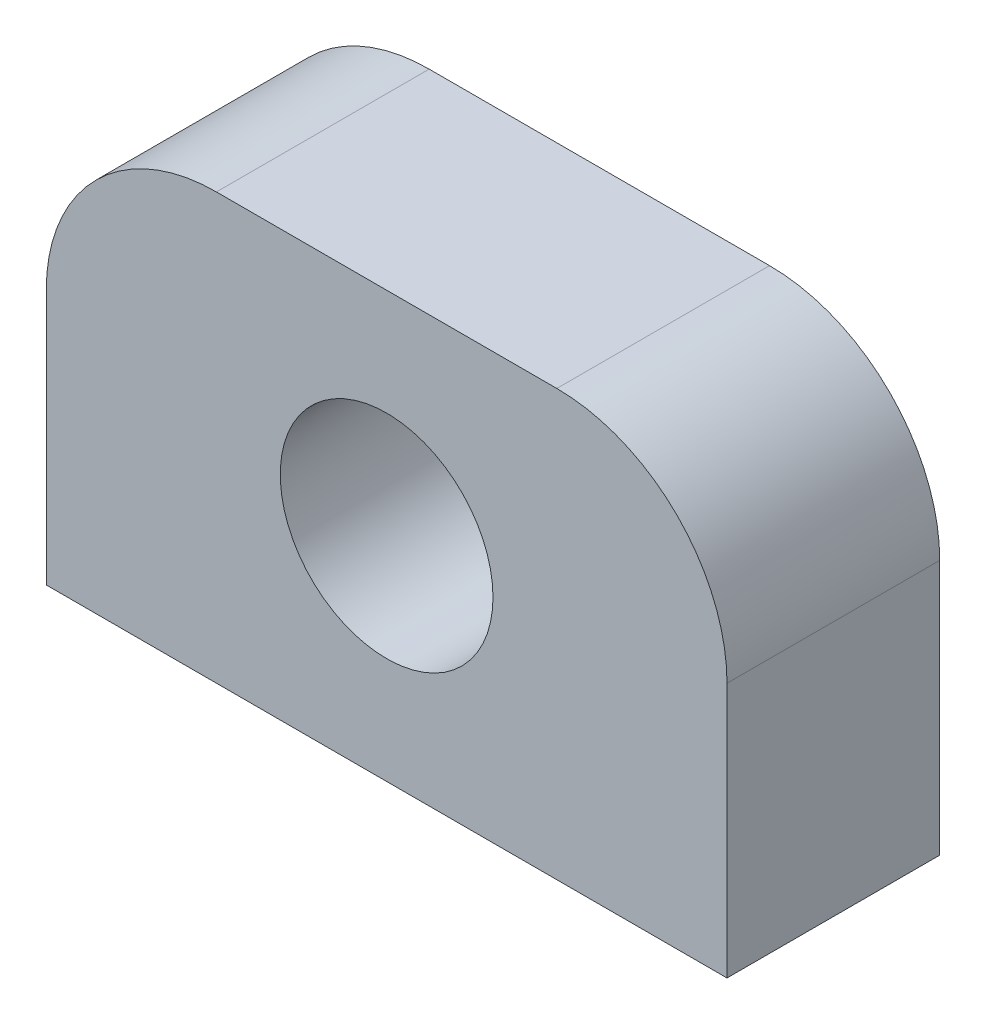
SolidWorks part; units mm, degrees
ref_plane "Front Plane" through (0, 0, 0) normal (0, 0, 1) x (1, 0, 0)
ref_plane "Top Plane" through (0, 0, 0) normal (0, 1, 0) x (1, 0, 0)
ref_plane "Right Plane" through (0, 0, 0) normal (1, 0, 0) x (0, 0, -1)
sketch "Sketch1" plane through (0, 0, 0) normal (0, 0, 1) x (1, 0, 0)
  line L0 (0, 0) -> (20.32, 12.7) construction
  line L1 (0, 0) -> (20.32, 0)
  line L2 (0, 0) -> (0, 7.62)
  line L3 (5.08, 12.7) -> (15.24, 12.7)
  line L4 (20.32, 0) -> (20.32, 7.62)
  line L5 (0, 12.7) -> (20.32, 0) construction
  circle A0 centre (10.16, 6.35) radius 3.175
  arc A1 (5.08, 12.7) -> (0, 7.62) centre (5.08, 7.62) ccw
  arc A2 (20.32, 7.62) -> (15.24, 12.7) centre (15.24, 7.62) ccw
  dimension "D3" = 6.35
  dimension "D4" = 5.08
  dimension "D5" = 5.08
  dimension "D1" = 12.7
  dimension "D2" = 20.32
extrude "Boss-Extrude1" add sketch "Sketch1" along normal blind 6.35
